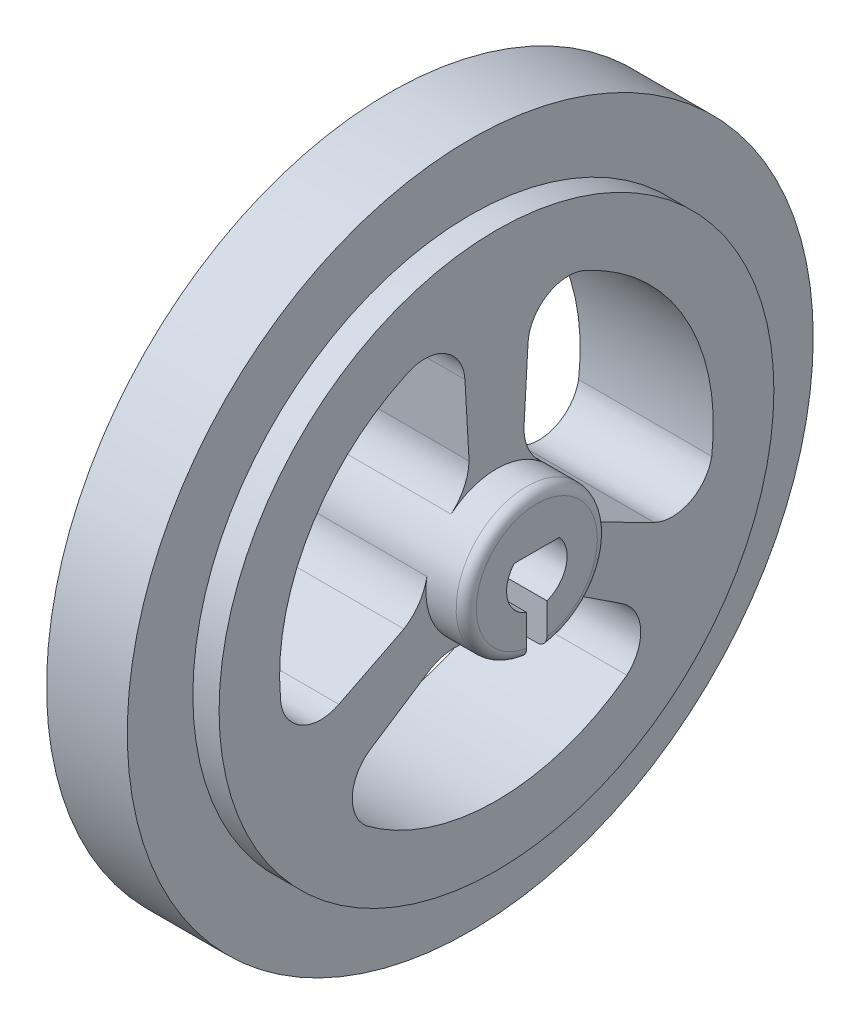
SolidWorks part; units mm, degrees
material "Borracha de silicone"
ref_plane "Plano frontal" through (0, 0, 0) normal (0, 0, 1) x (1, 0, 0)
ref_plane "Plano superior" through (0, 0, 0) normal (0, 1, 0) x (1, 0, 0)
ref_plane "Plano direito" through (0, 0, 0) normal (1, 0, 0) x (0, 0, -1)
sketch "Esboço1" plane through (0, 0, 0) normal (1, 0, 0) x (0, 0, -1)
  line L0 (1.118, 1) -> (-1.118, 1)
  line L1 (-0.5, -1.4142) -> (-0.5, -3.4641)
  line L2 (0.5, -1.4142) -> (0.5, -3.4641)
  line L3 (0, -1.5) -> (-1.0555, -1.5) construction
  line L4 (3.2296, -3.4333) -> (6.2449, -5.4106)
  line L5 (-1.3585, 4.5136) -> (-1.5633, 8.1136)
  line L6 (1.3585, 4.5136) -> (1.5633, 8.1136)
  line L7 (2.25, 2.681) -> (-2.25, 2.681) construction
  line L8 (4.5881, -1.0803) -> (7.8082, -2.703)
  line L9 (-4.5881, -1.0803) -> (-7.8082, -2.703)
  line L10 (-3.2296, -3.4333) -> (-6.2449, -5.4106)
  arc A0 (0.5, -3.4641) -> (-0.5, -3.4641) centre (0, 0) ccw
  circle A1 centre (0, 0) radius 13.75
  arc A2 (-1.118, 1) -> (-0.5, -1.4142) centre (0, 0) ccw
  arc A3 (0.5, -1.4142) -> (1.118, 1) centre (0, 0) ccw
  arc A4 (-4.5313, 9.7483) -> (-10.7079, -0.9499) centre (0, 0) ccw
  arc A5 (-1.5633, 8.1136) -> (-4.5313, 9.7483) centre (-3.56, 8) ccw
  arc A6 (1.5633, 8.1136) -> (4.5313, 9.7483) centre (3.56, 8) cw
  arc A7 (-2.25, 2.681) -> (-1.3585, 4.5136) centre (-3.8571, 4.5959) ccw
  arc A8 (2.25, 2.681) -> (1.3585, 4.5136) centre (3.8571, 4.5959) cw
  arc A9 (3.4468, 0.6081) -> (4.5881, -1.0803) centre (5.9088, 1.0424) ccw
  arc A10 (1.1968, -3.289) -> (3.2296, -3.4333) centre (2.0516, -5.6383) cw
  arc A11 (7.8082, -2.703) -> (10.671, -1.3011) centre (8.7082, -0.9169) ccw
  arc A12 (6.2449, -5.4106) -> (6.4623, -8.5908) centre (5.1482, -7.0831) cw
  arc A13 (-1.1968, -3.289) -> (-3.2296, -3.4333) centre (-2.0516, -5.6383) ccw
  arc A14 (-3.4468, 0.6081) -> (-4.5881, -1.0803) centre (-5.9088, 1.0424) cw
  arc A15 (-6.2449, -5.4106) -> (-6.4623, -8.5908) centre (-5.1482, -7.0831) ccw
  arc A16 (-7.8082, -2.703) -> (-10.7079, -0.9499) centre (-8.7082, -0.9169) cw
  arc A17 (-6.4623, -8.5908) -> (6.4623, -8.5908) centre (0, 0) ccw
  arc A18 (10.671, -1.3011) -> (4.5313, 9.7483) centre (0, 0) ccw
  point P50 (0, 0)
  dimension "D1" = 7
  dimension "D2" = 27.5
  dimension "D3" = 3
  dimension "D6" = 21.5
  dimension "D11" = 2.5
  dimension "D8" = 2
  dimension "D9" = 8
  dimension "D4" = 0.5
  dimension "D5" = 2.5
  dimension "D7" = 3.6
  dimension "D10" = 4.5
  dimension "D12" = 1.1
  dimension "D13" = 3
extrude "Ressalto-extrusão1" add sketch "Esboço1" along normal blind 5.3 and the other way blind 3.3 contours A3 L2 A0 L1 A2 L0 region at (0, 1.0987, 0)
extrude "Ressalto-extrusão2" add sketch "Esboço1<3>" along normal mid plane 6.6 contours A1 A18 A11 L8 A9 A0 A10 L4 A12 A17 A15 L10 A13 A14 L9 A16 A4 A5 L5 A7 A8 L6 A6 region at (0, 0, 13.3611)
sketch "Esboço1<3>" plane through (0, 0, 0) normal (1, 0, 0) x (0, 0, -1) same geometry as "Esboço1"
fillet "Filete2" radius 0.5 3 edges at (-3.3, -3.3945, 0.8529) (-3.3, -3.3945, -0.8529) (5.3, 3.5, 0)
sketch "Esboço2" plane through (0, 0, 0) normal (1, 0, 0) x (0, 0, -1)
  circle A0 centre (0, 0) radius 13.75
  circle A1 centre (0, 0) radius 17
  dimension "D1" = 34
  dimension "D2" = 27.5
extrude "Ressalto-extrusão3" add sketch "Esboço2" along normal mid plane 4
